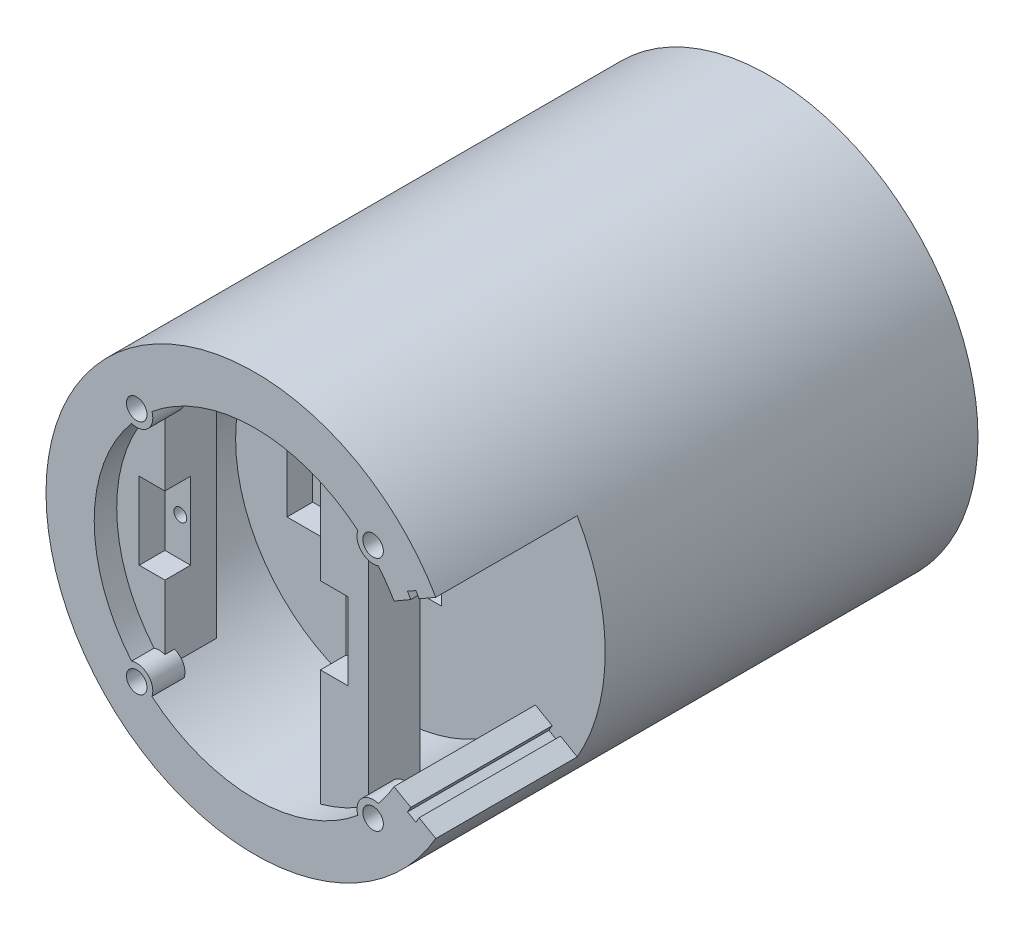
SolidWorks part; units mm, degrees
ref_plane "Спереди" through (0, 0, 0) normal (0, 0, 1) x (1, 0, 0)
ref_plane "Сверху" through (0, 0, 0) normal (0, 1, 0) x (1, 0, 0)
ref_plane "Справа" through (0, 0, 0) normal (1, 0, 0) x (0, 0, -1)
sketch "Эскиз1" plane through (0, 0, 0) normal (0, 0, 1) x (1, 0, 0)
  circle A1 centre (0, 0) radius 32.5
  dimension "D1" = 65
extrude "Бобышка-Вытянуть1" add sketch "Эскиз1" along normal blind 80
sketch "Эскиз3" plane through (0, 0, 0) normal (0, 0, -1) x (-1, 0, 0)
  circle A0 centre (0, 0) radius 22.5
  dimension "D1" = 45
extrude "Вырез-Вытянуть1" cut sketch "Эскиз3" against normal blind 50 contours A0
sketch "Эскиз10" plane through (0, 0, 50) normal (0, 0, -1) x (-1, 0, 0)
  circle A0 centre (0, 0) radius 15
  dimension "D1" = 30
sketch "Эскиз4" plane through (0, 0, 80) normal (0, 0, 1) x (1, 0, 0)
  circle A0 centre (0, 0) radius 25
  dimension "D1" = 50
extrude "Вырез-Вытянуть2" cut sketch "Эскиз4" against normal offset from surface (22 mm away) 8 up to face at (-22.5, 0, 50)
sketch "Эскиз13" plane through (0, 0, 58) normal (0, 0, 1) x (1, 0, 0)
  line L0 (0, 32.5) -> (0, -32.5) construction
  line L1 (-32.5, 0) -> (32.5, 0) construction
  line L3 (-17, 6.5) -> (7, 6.5)
  line L4 (-17, 6.5) -> (-17, -6.5)
  line L5 (-17, -6.5) -> (7, -6.5)
  line L6 (7, 6.5) -> (7, -6.5)
  circle A0 centre (0, 0) radius 32.5 construction
  point P11 (-17, 0)
  point P13 (-5, 6.5)
  dimension "D1" = 13
  dimension "D2" = 24
  dimension "D3" = 5
extrude "Вырез-Вытянуть3" cut sketch "Эскиз13" against normal blind 4
sketch "Эскиз12" plane through (0, 0, 80) normal (0, 0, 1) x (1, 0, 0)
  line L0 (0, 32.5) -> (0, -32.5) construction
  line L1 (0, 0) -> (28.1458, 16.25) construction
  line L2 (-32.5, 0) -> (32.5, 0) construction
  line L3 (28.1458, 16.25) -> (21.6506, 12.5)
  line L4 (28.1458, -16.25) -> (21.6506, -12.5)
  circle A0 centre (0, 0) radius 32.5 construction
  arc A1 (28.1458, -16.25) -> (28.1458, 16.25) centre (0, 0) ccw
  arc A2 (32.5, 0) -> (28.1458, 16.25) centre (0, 0) ccw
  arc A3 (21.6506, -12.5) -> (21.6506, 12.5) centre (0, 0) ccw
  circle M4 centre (0, 0) radius 32.5
  circle M9 centre (0, 0) radius 25
  dimension "D1" = 30
extrude "Вырез-Вытянуть4" cut sketch "Эскиз12" along direction (0, 0, -1) on the side against the normal up to surface (22 mm away) contours L4 A1 L3 M4 M9 region at (27.6099, 0, 80) up to face at (-25, 0, 58)
ref_plane "Плоскость2" through (0, 0, 68.5) normal (0, 0, 1) x (1, 0, 0)
sketch "Эскиз14" plane through (0, 0, 68.5) normal (0, 0, 1) x (1, 0, 0)
  line L1 (7, 0) -> (-46.5151, 0) construction
  line L2 (7, -6.5) -> (7, 6.5) construction
  line L3 (-17.5, -28.5313) -> (-17.5, 17.8536) construction
  line L6 (7, 0) -> (57.6607, 0) construction
  line L8 (14.2, -44.5711) -> (14.2, 20) construction
  line L10 (14.2, -20.5757) -> (14.2, 20.5757)
  line L13 (-17.5, -17.8536) -> (-17.5, 17.8536)
  line L15 (6.7, -24.0855) -> (6.7, 24.0855)
  line L16 (0, -28.5313) -> (0, 28.5313) construction
  arc A4 (-17.5, 17.8536) -> (-17.5, -17.8536) centre (0, 0) ccw
  arc A5 (14.2, 20.5757) -> (6.7, 24.0855) centre (0, 0) ccw
  arc A6 (6.7, -24.0855) -> (14.2, -20.5757) centre (0, 0) ccw
  point P11 (-17.5, 0)
  point P18 (7, 0)
  point P22 (14.2, 0)
  point P27 (14.2, 0)
  point P29 (-17.5, 0)
  point P33 (7.5, 0)
  point P34 (6.7, 0)
  point P35 (0, 0)
  dimension "D1" = 17.5
  dimension "D4" = 6.7
extrude "Бобышка-Вытянуть2" add sketch "Эскиз14" along normal blind 8
sketch "Эскиз15" plane through (0, 0, 76.5) normal (0, 0, 1) x (1, 0, 0)
  line L0 (43.3889, 0) -> (-43.3889, 0) construction
  line L1 (0, 36.1435) -> (0, -36.1435) construction
  line L2 (-21.5, 29.8665) -> (-21.5, -29.8665) construction
  line L3 (11, 32.0712) -> (11, -32.0712) construction
  line L4 (-17.5, 23.7559) -> (-17.5, -23.2484) construction
  line L5 (-21.5, -6) -> (-21.5, 6)
  line L6 (-21.5, 6) -> (-17.5, 6)
  line L7 (6.7, 41.39) -> (6.7, -19.4927) construction
  line L8 (6.7, 24.0855) -> (6.7, -24.0855) construction
  line L9 (11, -6) -> (11, 6)
  line L10 (11, 6) -> (6.7, 6)
  line L11 (-17.5, 6) -> (-17.5, -6)
  line L12 (6.7, 6) -> (6.7, -6)
  line L13 (11, -6) -> (6.7, -6)
  line L14 (-21.5, -6) -> (-17.5, -6)
  point P4 (0, 0)
  point P8 (0, 0)
  point P11 (-21.5, 0)
  point P14 (11, 0)
  point P19 (-17.5, 0.2537)
  point P24 (6.7, 10.9487)
  point P30 (6.7, 0)
  point P31 (11, 0)
  point P32 (-17.5, 0)
  point P33 (-21.5, 0)
  dimension "D1" = 21.5
  dimension "D2" = 11
  dimension "D3" = 6
  dimension "D4" = 6
extrude "Вырез-Вытянуть5" cut sketch "Эскиз15" along direction (0, 0, 1) on the side against the normal offset from surface (4 mm away) 18.5 up to face at (-5, 0, 54)
sketch "Эскиз17" plane through (0, 0, 72.5) normal (0, 0, 1) x (1, 0, 0)
  circle A1 centre (-19.1, 0) radius 1
  circle A2 centre (8.6, 0) radius 1
extrude "Вырез-Вытянуть6" cut sketch "Эскиз17" along direction (0, 0, 1) on the side against the normal up to surface (4 mm away) up to face at (10.5232, 0, 68.5)
sketch "Эскиз18" plane through (0, 0, 0) normal (0.5, -0.866, 0) x (0.866, 0.5, 0)
  line L0 (28.75, 80) -> (28.75, 56.0459) construction
  line L1 (32.5, 80) -> (25, 80) construction
  line L2 (29.5, 80) -> (28, 80)
  line L3 (28, 80) -> (28, 58)
  line L4 (32.5, 58) -> (16.25, 58) construction
  line L5 (28, 58) -> (29.5, 58)
  line L6 (29.5, 80) -> (29.5, 58)
  point P11 (28.75, 58)
  dimension "D1" = 0.75
extrude "Вырез-Вытянуть7" cut sketch "Эскиз18" against normal blind 1
sketch "Эскиз19" plane through (0, 0, 0) normal (0.5, 0.866, 0) x (0.866, -0.5, 0)
  line L0 (28.75, -80) -> (28.75, -58) construction
  line L1 (32.5, -80) -> (25, -80) construction
  line L2 (16.25, -58) -> (32.5, -58) construction
  line L3 (28, -80) -> (29.5, -80)
  line L4 (29.5, -80) -> (29.5, -58)
  line L5 (29.5, -58) -> (28, -58)
  line L6 (28, -80) -> (28, -58)
  dimension "D1" = 0.75
extrude "Вырез-Вытянуть8" cut sketch "Эскиз19" against normal blind 1
chamfer "Фаска1" distance 1 angle 45 1 edges at (-22.5, 0, 0)
sketch "Эскиз20" plane through (0, 0, 80) normal (0, 0, 1) x (1, 0, 0)
  line L0 (-57.2124, 0) -> (57.2124, 0) construction
  line L1 (0, 34.3681) -> (0, -34.3681) construction
  line L2 (0, 0) -> (-44.2288, 44.2288) construction
  circle A0 centre (0, 0) radius 25 construction
  circle A2 centre (0, 0) radius 26 construction
  circle A3 centre (-18.3848, 18.3848) radius 2.5
  circle A4 centre (18.3848, 18.3848) radius 2.5
  circle A5 centre (18.3848, -18.3848) radius 2.5
  circle A6 centre (-18.3848, -18.3848) radius 2.5
  point P8 (0, 0)
  point P12 (0, 0)
  point P27 (0, 0)
  dimension "D2" = 52
  dimension "D3" = 5
  dimension "D1" = 45
  dimension "D4" = 4
extrude "Бобышка-Вытянуть3" add sketch "Эскиз20" against normal blind 5
sketch "Эскиз21" plane through (0, 0, 80) normal (0, 0, 1) x (1, 0, 0)
  circle A0 centre (-18.3848, 18.3848) radius 1.6
  circle A1 centre (18.3848, 18.3848) radius 1.6
  circle A2 centre (18.3848, -18.3848) radius 1.6
  circle A3 centre (-18.3848, -18.3848) radius 1.6
  point P12 (0, 0)
  dimension "D1" = 3.2
  dimension "D2" = 4
extrude "Вырез-Вытянуть9" cut sketch "Эскиз21" against normal blind 5
